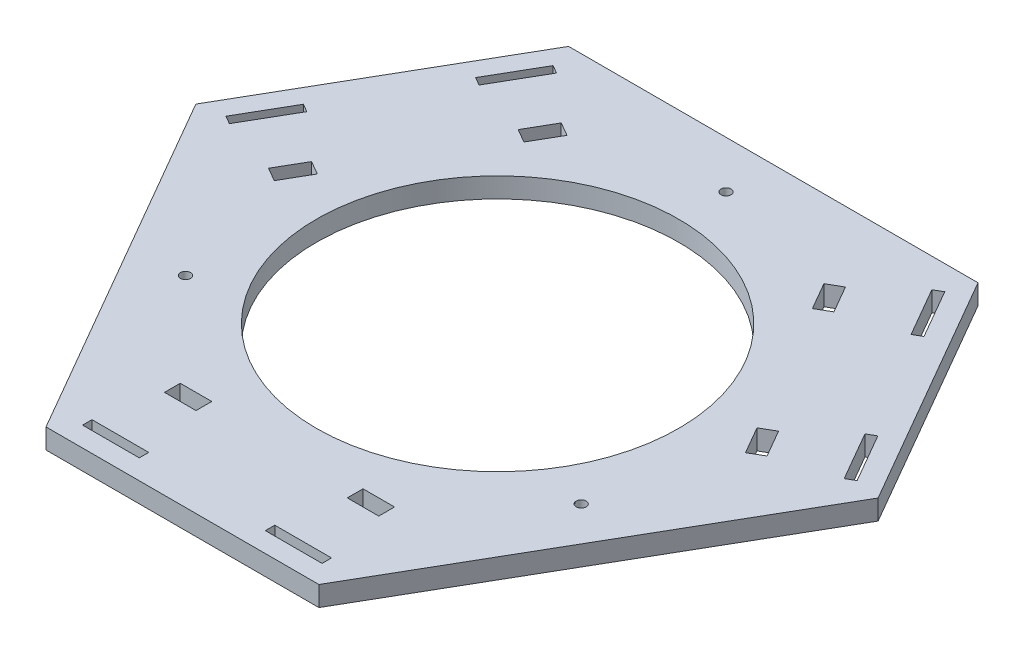
SolidWorks part; units mm, degrees
ref_plane "Front Plane" through (0, 0, 0) normal (0, 0, 1) x (1, 0, 0)
ref_plane "Top Plane" through (0, 0, 0) normal (0, 1, 0) x (1, 0, 0)
ref_plane "Right Plane" through (0, 0, 0) normal (1, 0, 0) x (0, 0, -1)
sketch "Sketch1" plane through (0, 0, 0) normal (0, 1, 0) x (1, 0, 0)
  line L0 (0, 200) -> (-173.2051, -100)
  line L1 (-173.2051, -100) -> (173.2051, -100)
  line L2 (173.2051, -100) -> (0, 200)
  line L4 (0, -175) -> (151.5544, 87.5)
  line L5 (151.5544, 87.5) -> (-151.5544, 87.5)
  line L6 (-151.5544, 87.5) -> (0, -175)
  circle A0 centre (0, 0) radius 200 construction
  circle A1 centre (0, 0) radius 100 construction
  circle A2 centre (0, 0) radius 175 construction
  circle A3 centre (0, 0) radius 87.5 construction
  dimension "D1" = 400
  dimension "D2" = 350
other "AlignGroup1"
extrude "Boss-Extrude1" add sketch "Sketch1" along normal blind 6.35 contours L0 L6 L1 L4 L2 L5 region at (0, 0, 0)
sketch "Sketch2" plane through (0, 6.35, 0) normal (0, 1, 0) x (1, 0, 0)
  line L0 (-43.3013, -100) -> (43.3013, -100) construction
  line L1 (-38, -90.7) -> (-20, -90.7)
  line L2 (-38, -90.7) -> (-38, -93.7)
  line L3 (-38, -93.7) -> (-20, -93.7)
  line L4 (-20, -90.7) -> (-20, -93.7)
  line L5 (0, -100) -> (0, 87.5) construction
  line L6 (64.9519, 87.5) -> (-64.9519, 87.5) construction
  line L7 (38, -90.7) -> (38, -93.7)
  line L8 (-86.6025, 50) -> (75.7772, -43.75) construction
  line L9 (-62.1466, 79.759) -> (-59.5485, 78.259)
  line L10 (20, -90.7) -> (20, -93.7)
  line L11 (-62.1466, 79.759) -> (-71.1466, 64.1705)
  line L12 (-71.1466, 64.1705) -> (-68.5485, 62.6705)
  line L13 (38, -93.7) -> (20, -93.7)
  line L14 (38, -90.7) -> (20, -90.7)
  line L15 (-59.5485, 78.259) -> (-68.5485, 62.6705)
  line L16 (-64.9519, 87.5) -> (-108.2532, 12.5) construction
  line L17 (43.3013, -100) -> (108.2532, 12.5) construction
  line L18 (-97.5485, 12.441) -> (-88.5485, 28.0295)
  line L19 (-91.1466, 29.5295) -> (-88.5485, 28.0295)
  line L20 (-100.1466, 13.941) -> (-91.1466, 29.5295)
  line L21 (-100.1466, 13.941) -> (-97.5485, 12.441)
  line L22 (86.6025, 50) -> (-75.7772, -43.75) construction
  line L23 (108.2532, 12.5) -> (64.9519, 87.5) construction
  line L24 (-108.2532, 12.5) -> (-43.3013, -100) construction
  line L25 (100.1466, 13.941) -> (91.1466, 29.5295)
  line L26 (59.5485, 78.259) -> (62.1466, 79.759)
  line L27 (59.5485, 78.259) -> (68.5485, 62.6705)
  line L28 (68.5485, 62.6705) -> (71.1466, 64.1705)
  line L29 (62.1466, 79.759) -> (71.1466, 64.1705)
  line L30 (88.5485, 28.0295) -> (91.1466, 29.5295)
  line L31 (97.5485, 12.441) -> (88.5485, 28.0295)
  line L32 (97.5485, 12.441) -> (100.1466, 13.941)
  line L33 (-24, -71.7) -> (-24, -66.7)
  line L34 (34, -71.7) -> (24, -71.7)
  line L35 (34, -71.7) -> (34, -66.7)
  line L36 (34, -66.7) -> (24, -66.7)
  line L37 (24, -71.7) -> (24, -66.7)
  line L38 (-34, -66.7) -> (-24, -66.7)
  line L39 (-34, -71.7) -> (-34, -66.7)
  line L40 (-34, -71.7) -> (-24, -71.7)
  line L41 (79.094, 6.4051) -> (74.094, 15.0654)
  line L42 (40.7639, 62.7949) -> (45.094, 65.2949)
  line L43 (40.7639, 62.7949) -> (45.7639, 54.1346)
  line L44 (45.7639, 54.1346) -> (50.094, 56.6346)
  line L45 (45.094, 65.2949) -> (50.094, 56.6346)
  line L46 (69.7639, 12.5654) -> (74.094, 15.0654)
  line L47 (74.7639, 3.9051) -> (69.7639, 12.5654)
  line L48 (74.7639, 3.9051) -> (79.094, 6.4051)
  line L49 (-74.7639, 3.9051) -> (-69.7639, 12.5654)
  line L50 (-45.094, 65.2949) -> (-40.7639, 62.7949)
  line L51 (-45.094, 65.2949) -> (-50.094, 56.6346)
  line L52 (-50.094, 56.6346) -> (-45.7639, 54.1346)
  line L53 (-40.7639, 62.7949) -> (-45.7639, 54.1346)
  line L54 (-74.094, 15.0654) -> (-69.7639, 12.5654)
  line L55 (-79.094, 6.4051) -> (-74.094, 15.0654)
  line L56 (-79.094, 6.4051) -> (-74.7639, 3.9051)
  point P4 (-29, -93.7)
  point P50 (29, -71.7)
  point P51 (29, -90.7)
  point P60 (64.0485, 70.4647)
  point P61 (47.594, 60.9647)
  point P70 (-47.594, 60.9647)
  dimension "D1" = 18
  dimension "D2" = 3
  dimension "D3" = 6.3
  dimension "D5" = 6.3
  dimension "D6" = 18
  dimension "D7" = 3
  dimension "D9" = 18
  dimension "D10" = 3
  dimension "D12" = 6.3
  dimension "D13" = 5
  dimension "D14" = 10
  dimension "D15" = 19
  dimension "D16" = 5
  dimension "D17" = 10
  dimension "D18" = 19
  dimension "D19" = 9
  dimension "D20" = 5
  dimension "D21" = 10
  dimension "D22" = 19
  dimension "D23" = 9
  dimension "D8" = 38
  dimension "D11" = 38
  dimension "D4" = 38
extrude "Cut-Extrude1" cut sketch "Sketch2" against normal through all
sketch "Sketch3" plane through (0, 6.35, 0) normal (0, 1, 0) x (1, 0, 0)
  point P0 (0, 0)
ref_axis "Axis1" through (0, 0, 0) along (0, 1, 0)
sketch "Sketch4" plane through (0, 6.35, 0) normal (0, 1, 0) x (1, 0, 0)
  circle A0 centre (0, 0) radius 57.5
  dimension "D1" = 115
extrude "Cut-Extrude2" cut sketch "Sketch4" against normal through all
sketch "Sketch5" plane through (0, 6.35, 0) normal (0, 1, 0) x (1, 0, 0)
  line L0 (0, 87.5) -> (0, 57.5) construction
  line L1 (64.9519, 87.5) -> (-64.9519, 87.5) construction
  line L2 (-75.7772, -43.75) -> (-62.7868, -36.25) construction
  line L4 (-108.2532, 12.5) -> (-43.3013, -100) construction
  line L6 (75.7772, -43.75) -> (62.7868, -36.25) construction
  line L7 (43.3013, -100) -> (108.2532, 12.5) construction
  circle A0 centre (0, 0) radius 57.5 construction
  circle A1 centre (0, 0) radius 72.5 construction
  circle A2 centre (0, 72.5) radius 1.6
  circle A3 centre (-62.7868, -36.25) radius 1.6
  circle A4 centre (62.7868, -36.25) radius 1.6
  point P10 (0, 72.5)
  dimension "D1" = 3.2
extrude "Cut-Extrude3" cut sketch "Sketch5" against normal through all
equation "\"D19@Sketch2\"=\"D9@Sketch2\"/2"
equation "\"D23@Sketch2\"=\"D6@Sketch2\"/2"
